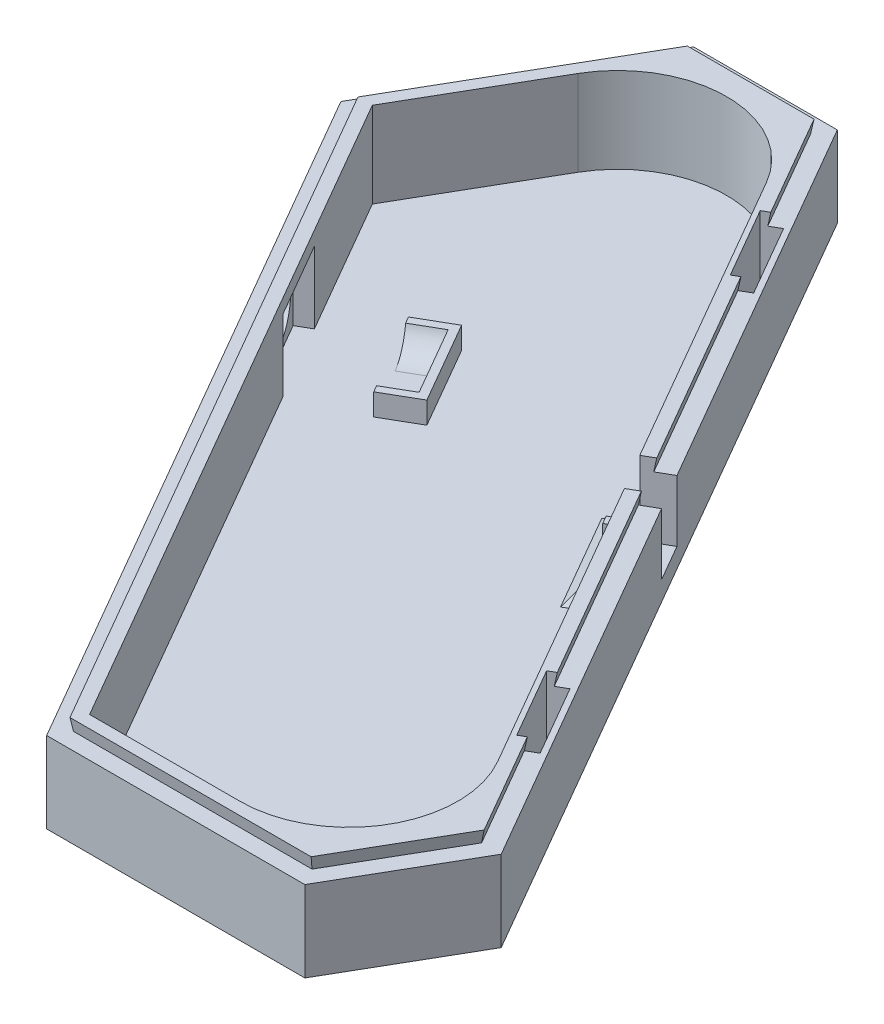
SolidWorks part; units mm, degrees
ref_plane "Plan de face" through (0, 0, 0) normal (0, 0, 1) x (1, 0, 0)
ref_plane "Plan de dessus" through (0, 0, 0) normal (0, 1, 0) x (1, 0, 0)
ref_plane "Plan de droite" through (0, 0, 0) normal (1, 0, 0) x (0, 0, -1)
sketch "Esquisse1" plane through (0, 0, 0) normal (0, 1, 0) x (1, 0, 0)
  line L3 (-77.5, -44.7446) -> (77.5, -44.7446)
  line L4 (77.5, -44.7446) -> (0, 89.4893)
  line L5 (0, 89.4893) -> (-77.5, -44.7446)
  line L6 (0, 89.4893) -> (0, -44.7446) construction
  line L7 (77.5, -44.7446) -> (-38.75, 22.3723) construction
  dimension "D1" = 155
extrude "Boss.-Extru.1" add sketch "Esquisse1" along normal blind 12 separate body
ref_axis "Axe1" through (0, -0.9, 0) along (0, 1, 0)
sketch "Esquisse2" plane through (0, 12, 0) normal (0, 1, 0) x (1, 0, 0)
  line L0 (-9.2376, 73.4893) -> (9.2376, 73.4893)
  line L1 (0, 89.4893) -> (-77.5, -44.7446) construction
  line L2 (77.5, -44.7446) -> (0, 89.4893) construction
  line L3 (9.2376, 73.4893) -> (0, 89.4893)
  line L4 (0, 89.4893) -> (-9.2376, 73.4893)
  line L5 (77.5, -44.7446) -> (68.2624, -28.7446)
  line L6 (68.2624, -28.7446) -> (59.0248, -44.7446)
  line L7 (59.0248, -44.7446) -> (77.5, -44.7446)
  line L8 (-77.5, -44.7446) -> (25.8333, -44.7446)
  line L9 (25.8333, -44.7446) -> (-25.8333, 44.7446)
  line L10 (-25.8333, 44.7446) -> (-77.5, -44.7446)
  line L11 (-77.5, -44.7446) -> (77.5, -44.7446) construction
  point P6 (0, 73.4893)
  point P17 (0, 0)
  dimension "D1" = 16
  dimension "D3" = 16
extrude "Enlèv. mat.-Extru.1" cut sketch "Esquisse2" against normal through all
sketch "Esquisse3" plane through (0, 12, 0) normal (0, 1, 0) x (1, 0, 0)
  line L3 (12.1244, 61.4893) -> (-12.1244, 61.4893) construction
  line L4 (59.3135, -20.2446) -> (12.1244, 61.4893)
  line L5 (-12.1244, 61.4893) -> (-21.7919, 44.7446)
  line L10 (-9.2376, 73.4893) -> (9.2376, 73.4893) construction
  line L11 (27.8541, -41.2446) -> (47.1891, -41.2446)
  line L12 (59.0132, -34.7407) -> (-47.6968, 28.0788) construction
  line L13 (0, -41.6074) -> (0, 68.4893) construction
  line L14 (47.9131, 27.5989) -> (-59.0132, -34.7407) construction
  line L15 (-9.2376, 73.4893) -> (-25.8333, 44.7446) construction
  line L16 (68.2624, -28.7446) -> (9.2376, 73.4893) construction
  line L17 (25.8333, -44.7446) -> (59.0248, -44.7446) construction
  line L18 (27.8541, -41.2446) -> (-21.7919, 44.7446)
  line L20 (25.8333, -44.7446) -> (-25.8333, 44.7446) construction
  arc A3 (12.1244, 61.4893) -> (-12.1244, 61.4893) centre (0, 54.4893) ccw
  arc A4 (47.1891, -41.2446) -> (59.3135, -20.2446) centre (47.1891, -27.2446) ccw
  arc A6 (-59.3135, -20.2446) -> (-59.0132, -34.7407) centre (-47.1891, -27.2446) ccw [skipped]
  point P23 (0, 0)
  dimension "D2" = 14
  dimension "D1" = 3.5
  dimension "D4" = 3.5
  dimension "D5" = 3.5
  dimension "D6" = 3.5
  dimension "D3" = 3
extrude "Enlèv. mat.-Extru.2" cut sketch "Esquisse3" against normal blind 11
sketch "Esquisse4" plane through (0, 12, 0) normal (0, 1, 0) x (1, 0, 0)
  line L0 (37.0689, 18.2841) -> (34.3689, 22.9606)
  line L1 (59.3135, -20.2446) -> (12.1244, 61.4893) construction
  line L2 (34.3689, 22.9606) -> (37.4, 24.7106)
  line L3 (68.2624, -28.7446) -> (9.2376, 73.4893) construction
  line L4 (37.4, 24.7106) -> (40.1, 20.0341)
  line L5 (40.1, 20.0341) -> (37.0689, 18.2841)
  point P9 (38.75, 22.3723)
  point P10 (38.75, 22.3723)
  point P21 (0, 0)
  dimension "D1" = 5.4
extrude "Enlèv. mat.-Extru.3" cut sketch "Esquisse4" against normal blind 9.5
ref_plane "Plan4" through (0, 0, 0) normal (0.5, 0, 0.866) x (0.866, 0, -0.5)
ref_plane "Plan5" through (0, 6.5, 0) normal (0, 1, 0) x (1, 0, 0)
sketch "Esquisse14" plane through (0, 1, 0) normal (0, 1, 0) x (1, 0, 0)
  line L4 (34.3689, 22.9606) -> (37.0689, 18.2841) construction
  line L5 (35.7189, 20.6223) -> (35.1993, 20.3223) construction
  line L6 (59.3135, -20.2446) -> (12.1244, 61.4893) construction
  line L7 (32.6993, 24.6524) -> (37.6993, 15.9922)
  line L8 (32.6993, 24.6524) -> (30.9672, 23.6524)
  line L9 (37.6993, 15.9922) -> (35.9672, 14.9922)
  line L10 (30.9672, 23.6524) -> (35.9672, 14.9922)
  line L11 (59.3135, -20.2446) -> (12.1244, 61.4893) construction
  dimension "D1" = 10
  dimension "D2" = 2
  dimension "D3" = 0.6
extrude "Boss.-Extru.6" add sketch "Esquisse14" along normal blind 2.2
sketch "Esquisse19" plane through (0, 2.5, 0) normal (0, 1, 0) x (1, 0, 0)
  line L0 (34.3689, 22.9606) -> (37.0689, 18.2841)
  line L1 (34.3689, 22.9606) -> (33.8493, 22.6606)
  line L2 (37.0689, 18.2841) -> (36.5493, 17.9841)
  line L3 (33.8493, 22.6606) -> (36.5493, 17.9841)
  line L4 (37.6993, 15.9922) -> (32.6993, 24.6524) construction
extrude "Boss.-Extru.8" add sketch "Esquisse19" against normal up to surface (1.5 mm away) up to face at (19.7712, 1, -11.4149)
sketch "Esquisse15" plane through (0, 3.2, 0) normal (0, 1, 0) x (1, 0, 0)
  line L0 (35.1591, 20.9919) -> (35.7591, 19.9527)
  line L1 (35.1591, 20.9919) -> (33.1672, 19.8419)
  line L2 (35.7591, 19.9527) -> (33.7672, 18.8027)
  line L3 (33.1672, 19.8419) -> (33.7672, 18.8027)
  line L5 (30.9672, 23.6524) -> (35.9672, 14.9922) construction
  line L8 (37.6993, 15.9922) -> (32.6993, 24.6524) construction
  line L9 (35.4591, 20.4723) -> (35.1993, 20.3223) construction
  dimension "D1" = 1.2
  dimension "D2" = 0.3
extrude "Boss.-Extru.7" add sketch "Esquisse15" along normal blind 3 and the other way up to surface (2.2 mm away) other way up to face at (28.414, 1, -16.4048)
chamfer "Chanfrein3" distance 2.2 angle 45 3 edges at (33.4672, 1, -19.3223) (36.8333, 1, -15.4922) (31.8333, 1, -24.1524)
sketch "Esquisse17" plane through (0, 12, 0) normal (0, 1, 0) x (1, 0, 0)
  line L0 (37.4, 24.7106) -> (9.2376, 73.4893) construction
  line L1 (-9.2376, 73.4893) -> (9.2376, 73.4893) construction
  line L2 (-9.2376, 73.4893) -> (-25.8333, 44.7446) construction
  line L3 (-9.2376, 73.4893) -> (-25.8333, 44.7446) construction
  line L4 (25.8333, -44.7446) -> (-25.8333, 44.7446) construction
  line L5 (25.8333, -44.7446) -> (59.0248, -44.7446) construction
  line L6 (25.8333, -44.7446) -> (59.0248, -44.7446) construction
  line L7 (68.2624, -28.7446) -> (59.0248, -44.7446) construction
  line L8 (68.2624, -28.7446) -> (40.1, 20.0341) construction
  line L9 (37.4, 24.7106) -> (9.2376, 73.4893)
  line L10 (-9.2376, 73.4893) -> (9.2376, 73.4893)
  line L11 (-9.2376, 73.4893) -> (-25.8333, 44.7446)
  line L12 (-9.2376, 73.4893) -> (-25.8333, 44.7446)
  line L13 (25.8333, -44.7446) -> (-25.8333, 44.7446)
  line L14 (25.8333, -44.7446) -> (59.0248, -44.7446)
  line L15 (25.8333, -44.7446) -> (59.0248, -44.7446)
  line L16 (68.2624, -28.7446) -> (59.0248, -44.7446)
  line L17 (68.2624, -28.7446) -> (40.1, 20.0341)
extrude "Enlèv. de mat.-Extru.-Mince1" cut sketch "Esquisse17" against normal blind 1.6 draft 10 thin draft outward yes thin type one direction reverse wall 1.9
sketch "Esquisse18" plane through (0, 12, 0) normal (0, 1, 0) x (1, 0, 0)
  line L0 (38.75, 22.3723) -> (0, 0) construction
  line L5 (9.2376, 73.4893) -> (37.4, 24.7106) construction
  line L6 (57.6135, -16.1003) -> (59.5188, -15.0003)
  line L7 (40.1, 20.0341) -> (37.4, 24.7106) construction
  line L8 (54.2688, -5.907) -> (59.5188, -15.0003)
  line L21 (52.3635, -7.007) -> (54.2688, -5.907)
  line L22 (20.1135, 48.8516) -> (14.8635, 57.9449)
  line L23 (20.1135, 48.8516) -> (22.0188, 49.9516)
  line L24 (22.0188, 49.9516) -> (16.7688, 59.0449)
  line L25 (14.8635, 57.9449) -> (16.7688, 59.0449)
  line L30 (52.3635, -7.007) -> (57.6135, -16.1003)
  point P4 (19.3938, 54.4983)
  dimension "D1" = 75
  dimension "D2" = 2.2
  dimension "D3" = 10.5
  dimension "D4" = 0.7
extrude "Enlèv. mat.-Extru.10" cut sketch "Esquisse18" against normal up to surface (11 mm away) up to face at (28.1419, 1, -16.2477)
sketch "Esquisse16" plane through (0, 0, 0) normal (0, 1, 0) x (1, 0, 0)
  line L0 (11.2217, 27.4997) -> (41.3465, -26.6864)
  line L1 (-19.3685, 82.5231) -> (-119.2403, 26.9993)
  line L2 (72.2349, -82.2461) -> (-27.6369, -137.7698)
  line L3 (-119.2403, 26.9993) -> (-27.6369, -137.7698)
  line L4 (-19.3685, 82.5231) -> (51.5403, 121.9449)
  line L6 (51.5403, 121.9449) -> (82.1306, 66.9215)
  line L7 (11.2217, 27.4997) -> (82.1306, 66.9215)
  line L8 (72.2349, -82.2461) -> (117.9546, -56.8282)
  line L10 (117.9546, -56.8282) -> (87.0662, -1.2686)
  line L11 (41.3465, -26.6864) -> (87.0662, -1.2686)
extrude "Enlèv. mat.-Extru.9" [suppressed] cut sketch "Esquisse16" along normal through all
sketch "Esquisse20" plane through (0, 0, 0) normal (-0.866, 0, 0.5) x (0.5, 0, 0.866)
  line L0 (51.6667, 0) -> (-51.6667, 0) construction
  circle A0 centre (-25, 5.5) radius 3.5
  dimension "D1" = 7
  dimension "D3" = 25
  dimension "D2" = 5.5
extrude "Enlèv. mat.-Extru.11" cut sketch "Esquisse20" against normal blind 10
sketch "Esquisse21" plane through (3.0311, 0, -1.75) normal (0.866, 0, -0.5) x (-0.5, 0, -0.866)
  line L0 (49.6459, 1) -> (-49.6459, 1) construction
  line L1 (18.3, 10.2) -> (29.3, 10.2)
  line L2 (18.3, 10.2) -> (18.3, 1)
  line L3 (18.3, 1) -> (29.3, 1)
  line L4 (29.3, 10.2) -> (29.3, 1)
  circle A0 centre (25, 5.5) radius 3.5 construction
  dimension "D1" = 11
  dimension "D2" = 9.2
  dimension "D3" = 6.7
extrude "Enlèv. mat.-Extru.12" cut sketch "Esquisse21" against normal blind 2
sketch "Esquisse22" plane through (0, 1, 0) normal (0, 1, 0) x (1, 0, 0)
  line L5 (-3.5979, 30.8317) -> (-0.1338, 32.8317)
  line L6 (-0.1338, 32.8317) -> (4.9662, 23.9983)
  line L7 (-21.7919, 44.7446) -> (27.8541, -41.2446) construction
  line L8 (4.9662, 23.9983) -> (1.5021, 21.9983)
  point P5 (-3.5859, 31.6811)
  point P6 (3.0311, 1.75)
  dimension "D1" = 10.2
  dimension "D2" = 4
  dimension "D3" = 12.8
  dimension "D4" = 18.3
extrude "Extru.-Mince1" add sketch "Esquisse22" along normal blind 2.8 thin thin type one direction reverse wall 1
fillet "Congé1" radius 3.85 1 edges at (-1.8658, 1, -31.8317)
equation "\"D6@Esquisse3\"=\"D4@Esquisse3\""
equation "\"D1@Esquisse3\"=\"D4@Esquisse3\""
